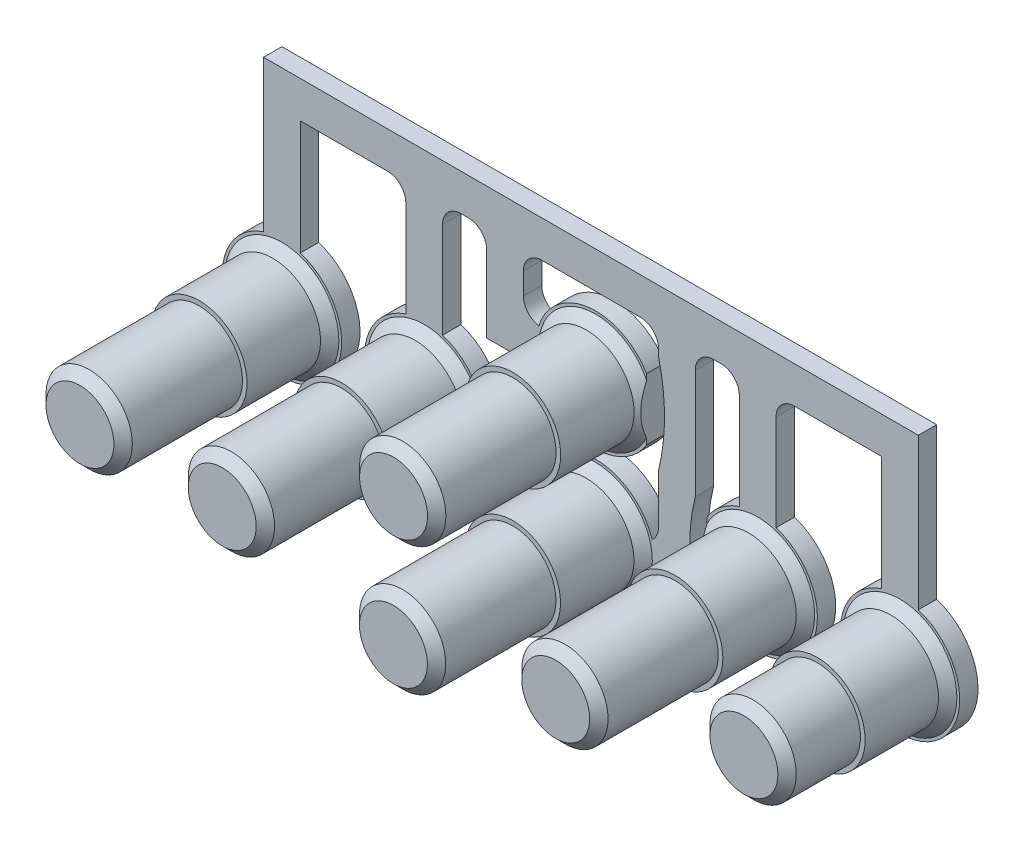
SolidWorks part; units mm, degrees
ref_plane "Front Plane" through (0, 0, 0) normal (0, 0, 1) x (1, 0, 0)
ref_plane "Top Plane" through (0, 0, 0) normal (0, 1, 0) x (1, 0, 0)
ref_plane "Right Plane" through (0, 0, 0) normal (1, 0, 0) x (0, 0, -1)
sketch "Skizze1" plane through (0, 0, 0) normal (0, 0, 1) x (1, 0, 0)
  line L0 (0.0076, 9.9935) -> (0.0076, 3.9935) construction
  line L1 (-2.9924, 9.9935) -> (3.0076, 9.9935) construction
  line L2 (3.0076, 3.9935) -> (-2.9924, 3.9935) construction
  line L3 (8.8392, 4.8386) -> (8.8392, -1.1614) construction
  line L4 (5.8392, 4.8386) -> (11.8392, 4.8386) construction
  line L5 (11.8392, -1.1614) -> (5.8392, -1.1614) construction
  line L6 (16.5862, 4.8386) -> (16.5862, -1.1614) construction
  line L7 (13.5862, 4.8386) -> (19.5862, 4.8386) construction
  line L8 (19.5862, -1.1614) -> (13.5862, -1.1614) construction
  line L9 (-9.3218, 4.8386) -> (-9.3218, -1.1614) construction
  line L10 (-12.3218, 4.8386) -> (-6.3218, 4.8386) construction
  line L11 (-6.3218, -1.1614) -> (-12.3218, -1.1614) construction
  line L12 (-17.0688, 4.8386) -> (-17.0688, -1.1614) construction
  line L13 (-20.0688, 4.8386) -> (-14.0688, 4.8386) construction
  line L14 (-14.0688, -1.1614) -> (-20.0688, -1.1614) construction
  circle A0 centre (0, 0) radius 2.35
  circle A1 centre (0.0076, 6.9935) radius 2.35
  circle A2 centre (8.8392, 1.8386) radius 2.35
  circle A3 centre (16.5862, 1.8386) radius 2.35
  circle A4 centre (-9.3218, 1.8386) radius 2.35
  circle A5 centre (-17.0688, 1.8386) radius 2.35
  dimension "D2" = 4.7
extrude "Aufsatz-Linear austragen1" add sketch "Skizze1" along normal blind 12 contours A5 | A4 | A0 | A1 | A2 region at (0, 0, 0) region at (0.0076, 6.9935, 0) region at (8.8392, 1.8386, 0) region at (-9.3218, 1.8386, 0) region at (-17.0688, 1.8386, 0)
extrude "Aufsatz-Linear austragen4" add sketch "Skizze1<3>" along normal blind 9.5 contours A3 region at (16.5862, 1.8386, 0)
sketch "Skizze1<3>" plane through (0, 0, 0) normal (0, 0, 1) x (1, 0, 0) same geometry as "Skizze1"
sketch "Skizze2" plane through (0, 0, 0) normal (0, 0, 1) x (1, 0, 0)
  circle A0 centre (-17.0688, 1.8386) radius 3.25
  circle A1 centre (-9.3218, 1.8386) radius 3.25
  circle A2 centre (0, 0) radius 3.25
  circle A3 centre (0.0076, 6.9935) radius 3.25
  circle A4 centre (8.8392, 1.8386) radius 3.25
  circle A5 centre (16.5862, 1.8386) radius 3.25
  dimension "D1" = 6.5
extrude "Aufsatz-Linear austragen2" add sketch "Skizze2" along normal blind 1
sketch "Skizze3" plane through (0, 0, 0) normal (0, 0, 1) x (1, 0, 0)
  line L0 (-17.0688, 1.8386) -> (-17.0688, 14.2266) construction
  line L1 (-18.0688, 13.1646) -> (-18.0688, 4.9309)
  line L2 (16.5862, 1.8386) -> (16.5862, 15.6024) construction
  line L3 (-18.0688, 13.1646) -> (17.5862, 13.1646)
  line L4 (17.5862, 13.1646) -> (17.5862, 4.9309)
  line L5 (-16.0688, 11.1646) -> (-16.0688, 4.9309)
  line L6 (-17.0688, 12.1646) -> (16.5862, 12.1646) construction
  line L7 (-16.0688, 11.1646) -> (-10.3218, 11.1646)
  line L8 (15.5862, 11.1646) -> (15.5862, 4.9309)
  line L9 (-16.0688, 11.1646) -> (-16.0688, 13.1646) construction
  line L10 (-9.3218, 1.8386) -> (-9.3218, 15.4604) construction
  line L11 (-8.3218, 11.1646) -> (-8.3218, 4.9309)
  line L12 (-10.3218, 11.1646) -> (-10.3218, 4.9309)
  line L13 (-8.3218, 11.1646) -> (-5.9218, 11.1646)
  line L14 (-4.9218, 11.1646) -> (-4.9218, 0.7573) construction
  line L15 (0.0076, 6.9935) -> (-4.9218, 6.9935) construction
  line L16 (-3.9218, 7.9935) -> (-3.0848, 7.9935)
  line L17 (-5.9218, 5.9935) -> (-3.0848, 5.9935)
  line L18 (-3.9218, 7.9935) -> (-3.9218, 11.1646)
  line L19 (-5.9218, 5.9935) -> (-5.9218, 11.1646)
  line L20 (4.4392, 11.1646) -> (4.4392, -2.7981) construction
  line L21 (0, 0) -> (4.4392, 0) construction
  line L22 (3.4392, -1) -> (3.0923, -1)
  line L23 (3.4392, 1) -> (3.0923, 1)
  line L24 (3.4392, -1) -> (5.4392, -1)
  line L25 (3.4392, 1) -> (3.4392, 11.1646)
  line L26 (5.4392, 1) -> (5.4392, 11.1646)
  line L27 (5.4392, 1) -> (5.4392, -1)
  line L28 (-3.9218, 11.1646) -> (3.4392, 11.1646)
  line L29 (5.4392, 11.1646) -> (7.8392, 11.1646)
  line L30 (8.8392, 1.8386) -> (8.8392, 11.1646) construction
  line L31 (9.8392, 11.1646) -> (9.8392, 4.9309)
  line L32 (7.8392, 11.1646) -> (7.8392, 4.9309)
  line L33 (9.8392, 11.1646) -> (15.5862, 11.1646)
  line L34 (-18.0688, 4.9309) -> (-16.0688, 4.9309)
  line L35 (-10.3218, 4.9309) -> (-8.3218, 4.9309)
  line L36 (-3.0848, 7.9935) -> (-3.0848, 5.9935)
  line L37 (3.0923, 1) -> (3.0923, -1)
  line L38 (7.8392, 4.9309) -> (9.8392, 4.9309)
  line L39 (17.5862, 4.9309) -> (15.5862, 4.9309)
  circle A0 centre (-17.0688, 1.8386) radius 3.25 construction
  circle A1 centre (16.5862, 1.8386) radius 3.25 construction
  circle A2 centre (-9.3218, 1.8386) radius 3.25 construction
  circle A3 centre (0.0076, 6.9935) radius 3.25 construction
  circle A4 centre (0, 0) radius 3.25 construction
  circle A5 centre (8.8392, 1.8386) radius 3.25 construction
  point P16 (-16.0688, 12.1646)
  dimension "D1" = 2
  dimension "D2" = 1
  dimension "D3" = 2
  dimension "D4" = 2
  dimension "D5" = 2
  dimension "D6" = 2
  dimension "D7" = 2
  dimension "D8" = 2
  dimension "D9" = 2
  dimension "D10" = 2.4
  dimension "D11" = 2.4
extrude "Aufsatz-Linear austragen3" add sketch "Skizze3" along normal up to surface (1 mm away) up to face at (-14.7188, 1.8386, 1)
sketch "Skizze5" plane through (0, 0, 1) normal (0, 0, 1) x (1, 0, 0)
  circle A0 centre (-17.0688, 1.8386) radius 2.6
  circle A1 centre (-9.3218, 1.8386) radius 2.6
  circle A2 centre (0.0076, 6.9935) radius 2.6
  circle A3 centre (0, 0) radius 2.6
  circle A4 centre (8.8392, 1.8386) radius 2.6
  circle A5 centre (16.5862, 1.8386) radius 2.6
  dimension "D1" = 5.2
extrude "Aufsatz-Linear austragen5" add sketch "Skizze5" along normal blind 4.5
chamfer "Fase1" distance 0.5 angle 45 5 edges at (11.1892, 1.8386, 12) (2.3576, 6.9935, 12) (2.35, 0, 12) (-6.9718, 1.8386, 12) (-14.7188, 1.8386, 12)
chamfer "Fase2" distance 0.5 angle 45 6 edges at (19.1862, 1.8386, 1) (11.4392, 1.8386, 1) (2.6076, 6.9935, 1) (2.6, 0, 1) (-6.7218, 1.8386, 1) (-14.4688, 1.8386, 1)
chamfer "Fase3" distance 0.5 angle 45 1 edges at (18.9362, 1.8386, 9.5)
sketch "Skizze6" plane through (0, 0, 1) normal (0, 0, 1) x (1, 0, 0)
  line L0 (2.7892, 9.8014) -> (2.7892, 4.4432)
  line L1 (2.7892, 4.4432) -> (3.4392, 4.4432)
  line L2 (3.4392, 11.1646) -> (3.4392, 1) construction
  line L3 (2.7892, 9.8014) -> (3.4392, 9.8014)
  line L4 (6.0892, 4.1892) -> (6.0892, -0.6077)
  line L5 (6.0892, -0.6077) -> (5.4392, -0.6077)
  line L6 (5.4392, -1) -> (5.4392, 11.1646) construction
  line L7 (6.0892, 4.1892) -> (5.4392, 4.1892)
  arc A0 (3.4392, 9.8014) -> (3.4392, 4.4432) centre (-7.4412, 7.1223) cw
  arc A1 (5.4392, 4.1892) -> (5.4392, -0.6077) centre (14.8009, 1.7908) ccw
  dimension "D1" = 0.65
  dimension "D2" = 0.65
extrude "Schnitt-Linear austragen1" cut sketch "Skizze6" against normal through all and the other way blind 7
fillet "Verrundung1" radius 1 11 edges at (5.4392, -1, 0.5) (3.4392, 1, 0.5) (9.8392, 11.1646, 0.5) (7.8392, 11.1646, 0.5) (3.4392, 11.1646, 0.5) (5.4392, 11.1646, 0.5) (-10.3218, 11.1646, 0.5) (-8.3218, 11.1646, 0.5) (-3.9218, 7.9935, 0.5) (-3.9218, 11.1646, 0.5) (-5.9218, 11.1646, 0.5)
